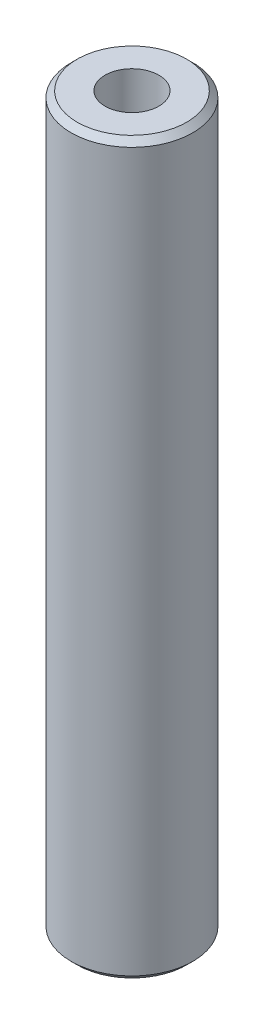
SolidWorks part; units mm, degrees
ref_plane "Front Plane" through (0, 0, 0) normal (0, 0, 1) x (1, 0, 0)
ref_plane "Top Plane" through (0, 0, 0) normal (0, 1, 0) x (1, 0, 0)
ref_plane "Right Plane" through (0, 0, 0) normal (1, 0, 0) x (0, 0, -1)
sketch "Sketch1" plane through (0, 0, 0) normal (0, 1, 0) x (1, 0, 0)
  circle A0 centre (0, 0) radius 50
  dimension "SHAFT_OD" = 100
extrude "Boss-Extrude1" add sketch "Sketch1" along normal blind 600
sketch "Sketch2" plane through (0, 0, 0) normal (0, 1, 0) x (1, 0, 0)
  circle A0 centre (0, 0) radius 22.1298
  dimension "BORE_D" = 44.2596
extrude "Cut-Extrude1" cut sketch "Sketch2" along normal through all
chamfer "Chamfer1" distance 5.0182 angle 45 2 edges at (0, 600, 50) (0, 0, 50)
